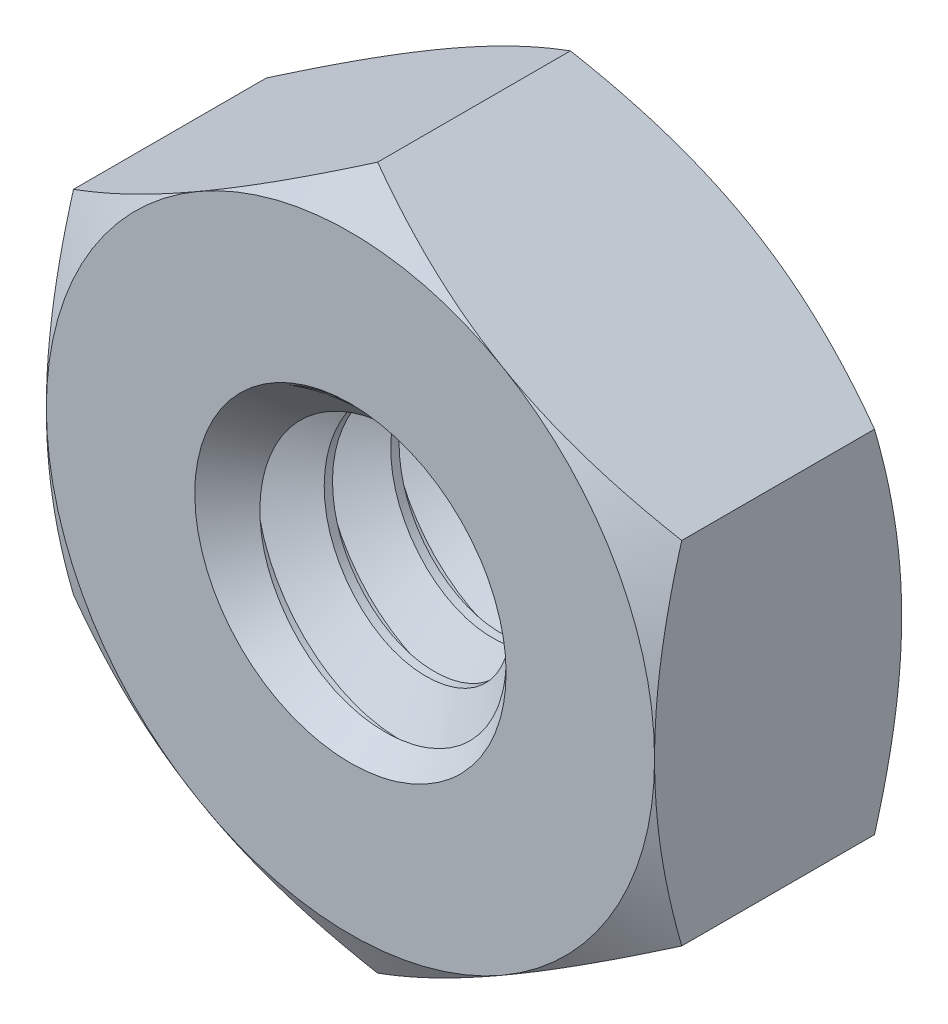
SolidWorks part; units mm, degrees
note: '?' marks a value the reader was unsure of.
other "Imported1" parameters "D1"=92.293, "Height"=1.3, "Width"=3.2, "Thread OD"=1.6, "D2"=0.0631, "Pitch"=0.35, "D3"=0.5154, "D4"=0.35
ref_plane "Front Plane" through (0, 0, 0) normal (0, 0, 1) x (1, 0, 0)
ref_plane "Top Plane" through (0, 0, 0) normal (0, 1, 0) x (1, 0, 0)
ref_plane "Right Plane" through (0, 0, 0) normal (1, 0, 0) x (0, 0, -1)
sketch "Sketch1" plane through (0, 0, 0) normal (1, 0, 0) x (0, 0, -1)
  line L0 (-0.65, 0) -> (0.65, 0) construction
  line L1 (-0.65, -1.6) -> (-0.65, 1.6) construction
  line L2 (0.65, -1.6) -> (0.65, 1.6) construction
  line L3 (-0.65, -0.8) -> (-0.65, 0.8) construction
  line L4 (-0.9781, 0.8379) -> (-0.8031, 0.5348) construction
  line L5 (-0.8031, 0.5348) -> (-0.6281, 0.8379) construction
  line L6 (-0.6281, 0.8379) -> (-0.9781, 0.8379) construction
  line L7 (-0.9672, 0.8189) -> (-0.6391, 0.8189) construction
  line L8 (-0.9563, 0.8) -> (-0.65, 0.8) construction
  line L9 (-0.825, 0.5727) -> (-0.7813, 0.5727) construction
  line L10 (-0.8031, 0.5727) -> (-0.8031, 0.5348) construction
  line L11 (-0.8031, 0.8379) -> (-0.8031, 0.8) construction
  point P4 (0, 0)
  point P7 (-0.65, 0)
  point P11 (0.65, 0)
  point P14 (-0.65, 0)
  point P26 (-0.8031, 0.8189)
  point P27 (-0.65, -0.8)
  dimension "D1" = 60
  dimension "D2" = 0.0437
sketch "Sketch2" plane through (0, 0, 0) normal (0, 0, 1) x (1, 0, 0)
  line L1 (0, 1.8475) -> (-1.6, 0.9238)
  line L2 (-1.6, 0.9238) -> (-1.6, -0.9238)
  line L3 (-1.6, -0.9238) -> (0, -1.8475)
  line L4 (0, -1.8475) -> (1.6, -0.9238)
  line L5 (1.6, -0.9238) -> (1.6, 0.9238)
  line L6 (1.6, 0.9238) -> (0, 1.8475)
  circle A0 centre (0, 0) radius 1.6 construction
  circle A1 centre (0, 0) radius 0.8
extrude "Boss-Extrude1" add sketch "Sketch2" along normal up to vertex (0.65 mm away) and the other way up to vertex (0.65 mm away) up to point (0, -1.6, 0.65) other way up to point (0, -1.6, -0.65)
sketch "Sketch3" plane through (0, 0, 0.65) normal (0, 0, 1) x (1, 0, 0)
  circle A0 centre (0, 0) radius 1.6
extrude "Cut-Extrude1" cut sketch "Sketch3" against normal through all draft 60 flip side to cut
mirror "Mirror1" about plane through (0, 0, 0) normal (0, 0, 1) of "Cut-Extrude1"
ref_axis "Center Axis 1" through (0, 0, -4.9461) along (0, 0, 1)?
ref_plane "Contact Plane 1" through (0, 0, 0.65) normal (0, 0, 1) x (1, 0, 0)
ref_plane "Contact Plane 2" through (0, 0, -0.65) normal (0, 0, -1) x (-1, 0, 0)
sketch "Sketch4" plane through (0, 0, 0) normal (1, 0, 0) x (0, 0, -1)
  line L1 (-0.9672, 0.8189) -> (-0.825, 0.5727)
  line L2 (-0.825, 0.5727) -> (-0.7813, 0.5727)
  line L3 (-0.7813, 0.5727) -> (-0.6391, 0.8189)
  line L4 (-0.9672, 0.8189) -> (-0.6391, 0.8189) construction
  line L5 (-0.9672, 0.8189) -> (-0.6391, 0.8189)
sketch "Sketch5" plane through (0, 0, 0.65) normal (0, 0, 1) x (1, 0, 0)
  circle A0 centre (0, 0) radius 0.8 construction
  circle A1 centre (0, 0) radius 0.8
curve "Helix/Spiral1" pitch 0.35 height 1.65 radius 0.8 centre (0, 0, 0.65) axis (0, 0, -1) start towards (0, 1, 0)
sweep "Sweep1" add profiles "Sketch4" path "Helix/Spiral1"
sketch "Sketch6" plane through (0, 0, 0.65) normal (0, 0, 1) x (1, 0, 0)
  circle A1 centre (0, 0) radius 0.8189
extrude "Cut-Extrude2" cut sketch "Sketch6" along normal through all and the other way through all draft 45
sketch "Sketch7" plane through (0, 0, -0.65) normal (0, 0, -1) x (-1, 0, 0)
  circle A1 centre (0, 0) radius 0.8189
  circle A2 centre (0, 0) radius 0.8189
  dimension "D1" = 0
extrude "Cut-Extrude3" cut sketch "Sketch7" along normal through all and the other way through all draft 45
equation "\"D2@Sketch1\"=\"Pitch@Sketch1\"/8"
equation "\"D4@Helix/Spiral1\"=\"Pitch@Sketch1\""
equation "\"D3@Helix/Spiral1\"=\"Height@Sketch1\"+\"Pitch@Sketch1\""
